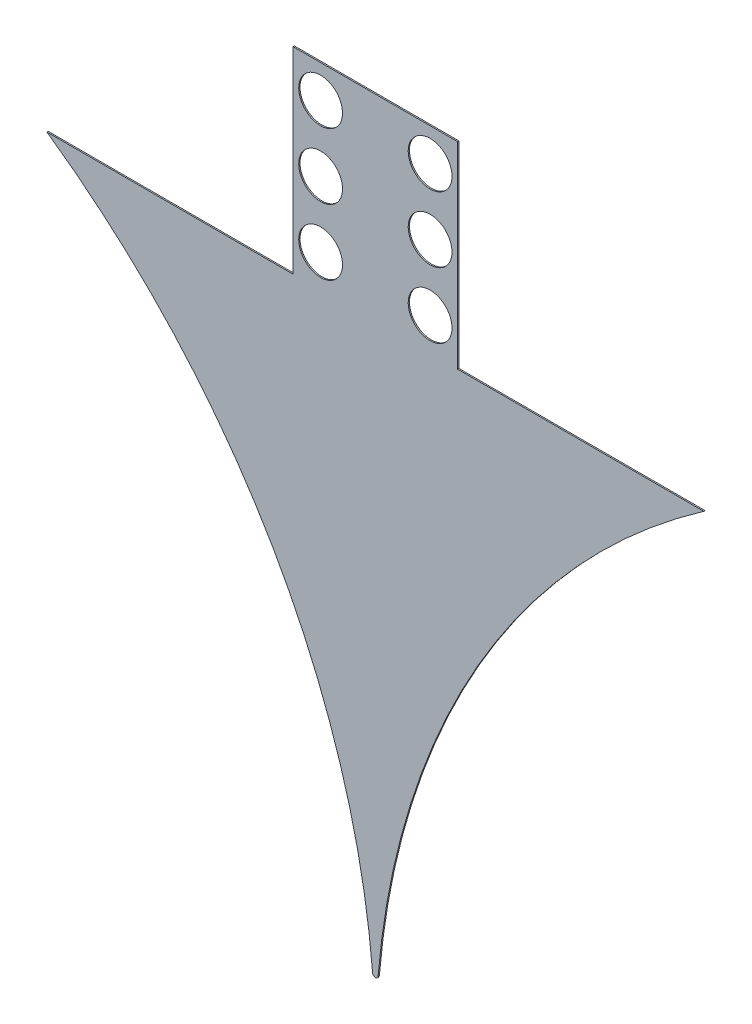
SolidWorks part; units mm, degrees
ref_plane "Front Plane" through (0, 0, 0) normal (0, 0, 1) x (1, 0, 0)
ref_plane "Top Plane" through (0, 0, 0) normal (0, 1, 0) x (1, 0, 0)
ref_plane "Right Plane" through (0, 0, 0) normal (1, 0, 0) x (0, 0, -1)
sketch "Sketch1" plane through (0, 0, 0) normal (0, 0, 1) x (1, 0, 0)
  line L0 (0, 145.9429) -> (0, -145.9429) construction
  line L1 (67, 50) -> (220, 50)
  line L2 (-67, 50) -> (-220, 50)
  line L3 (17.9555, 13) -> (15.1177, 40)
  line L4 (15.1177, 40) -> (12, 27.4955)
  line L5 (-15.1177, 40) -> (-12, 27.4955)
  line L6 (-17.9555, 13) -> (-15.1177, 40)
  line L7 (220, 50) -> (158.9525, 7.2541)
  line L8 (-220, 50) -> (-158.9525, 7.2541)
  line L9 (-140, -25) -> (-99.5632, -25)
  line L10 (140, -25) -> (99.5632, -25)
  arc A0 (67, 50) -> (17.9555, 13) centre (27.0477, 51.953) cw
  arc A1 (-67, 50) -> (-17.9555, 13) centre (-27.0477, 51.953) ccw
  arc A2 (12, 27.4955) -> (-12, 27.4955) centre (0, 0) ccw
  arc A3 (158.9525, 7.2541) -> (140, -25) centre (184.7635, -29.6077) ccw
  arc A4 (-99.5632, -25) -> (0, -115.6638) centre (-99.5632, -125) cw
  arc A5 (99.5632, -25) -> (0, -115.6638) centre (99.5632, -125) ccw
  arc A6 (-158.9525, 7.2541) -> (-140, -25) centre (-184.7635, -29.6077) cw
  dimension "D2" = 40
  dimension "D5" = 30
  dimension "D10" = 220
  dimension "D12" = 45
  dimension "D13" = 100
  dimension "D1" = 134
  dimension "D3" = 84
  dimension "D4" = 160
  dimension "D6" = 50
  dimension "D7" = 24
  dimension "D8" = 37
  dimension "D9" = 10
  dimension "D11" = 35
  dimension "D14" = 140
  dimension "D15" = 75
  dimension "D16" = 140
  dimension "D17" = 99.5632
sketch "Sketch2" plane through (0, 0, 0) normal (0, 0, 1) x (1, 0, 0)
  line L0 (0, 145.9429) -> (0, -145.9429) construction
  line L7 (0, 0) -> (0, -152.8683) construction
  line L8 (99.5632, -21.9265) -> (48.69, -83.15)
  line L9 (-99.5632, -21.9265) -> (-48.69, -83.15)
  line L26 (158.9525, 10.3276) -> (220, 53.0735)
  line L27 (220, 53.0735) -> (67, 53.0735)
  line L28 (17.9555, 16.0735) -> (15.1177, 43.0735)
  line L29 (15.1177, 43.0735) -> (12, 30.569)
  line L30 (-12, 30.569) -> (-15.1177, 43.0735)
  line L31 (-15.1177, 43.0735) -> (-17.9555, 16.0735)
  line L32 (-67, 53.0735) -> (-220, 53.0735)
  line L33 (-220, 53.0735) -> (-158.9525, 10.3276)
  line L34 (-140, -21.9265) -> (-99.5632, -21.9265)
  line L35 (99.5632, -21.9265) -> (140, -21.9265)
  circle A2 centre (46.19, 13) radius 1.5875
  circle A3 centre (-46.19, 13) radius 1.5875
  circle A4 centre (46.19, -80.65) radius 1.5875
  circle A5 centre (-46.19, -80.65) radius 1.5875
  arc A6 (48.69, -83.15) -> (0, -150) centre (70.2366, -150) ccw
  arc A7 (-48.69, -83.15) -> (0, -150) centre (-70.2366, -150) cw
  arc A14 (17.9555, 16.0735) -> (67, 53.0735) centre (27.0477, 55.0265) ccw
  arc A15 (12, 30.569) -> (-12, 30.569) centre (0, 3.0735) ccw
  arc A16 (-67, 53.0735) -> (-17.9555, 16.0735) centre (-27.0477, 55.0265) ccw
  arc A17 (-140, -21.9265) -> (-158.9525, 10.3276) centre (-184.7635, -26.5342) ccw
  arc A20 (158.9525, 10.3276) -> (140, -21.9265) centre (184.7635, -26.5342) ccw
  point P0 (0, 40)
  dimension "D3" = 93.65
  dimension "D4" = 3.175
  dimension "D5" = 3.175
  dimension "D6" = 3.175
  dimension "D7" = 3.175
  dimension "D2" = 40
  dimension "D9" = 25
  dimension "D10" = 46.19
  dimension "D11" = 27
  dimension "D12" = 46.19
  dimension "D13" = 99.5632
  dimension "D14" = 2.5
  dimension "D15" = 2.5
  dimension "D16" = 150
extrude "Boss-Extrude1" add sketch "Sketch2" along normal blind 0.118
sketch "Sketch3" plane through (0, 0, 0) normal (0, 0, -1) x (-1, 0, 0)
  line L0 (0, -121.719) -> (0, 0) construction
  line L1 (165, 49.5735) -> (165, 19.5735) construction
  line L2 (165, 19.5735) -> (165, 49.5735) construction
  line L3 (67, 53.0735) -> (220, 53.0735) construction
  circle A0 centre (165, 49.5735) radius 2
  circle A1 centre (165, 19.5735) radius 2
  circle A2 centre (150, 34.5735) radius 2
  dimension "D1" = 4
  dimension "D2" = 4
  dimension "D5" = 4
  dimension "D3" = 30
  dimension "D4" = 55
  dimension "D6" = 15
  dimension "D7" = 15
  dimension "D8" = 3.5
extrude "Cut-Extrude1" cut sketch "Sketch3" against normal through all
mirror "Mirror2" about plane through (0, 0, 0) normal (1, 0, 0) of "Cut-Extrude1"
chamfer "Chamfer1" distance 20 angle 90 2 edges at (-220, 53.0735, 0.059) (220, 53.0735, 0.059) first distance on face at (-143.5, 53.0735, 0.059) first distance on face at (143.5, 53.0735, 0.059)
sketch "Sketch4" plane through (0, 0, 0) normal (0, 0, -1) x (-1, 0, 0)
  line L11 (-225.9688, 80.922) -> (214.9402, 80.922)
  line L12 (-225.9688, 80.922) -> (-225.9688, -92.431)
  line L13 (-225.9688, -92.431) -> (214.9402, -92.431)
  line L14 (214.9402, 80.922) -> (214.9402, -92.431)
  point P0 (0, -150)
  dimension "D1" = 57.569
extrude "Cut-Extrude4" cut sketch "Sketch4" against normal through all contours L11 L14 L13 L12
sketch "Sketch5" plane through (0, 0, 0) normal (0, 0, -1) x (-1, 0, 0)
  line L0 (-30, -92.431) -> (30, -92.431) construction
  line L1 (-7.5, -74.431) -> (7.5, -74.431)
  line L2 (-7.5, -74.431) -> (-7.5, -92.431)
  line L3 (-7.5, -92.431) -> (7.5, -92.431)
  line L4 (7.5, -74.431) -> (7.5, -92.431)
  line L5 (-7.5, -74.431) -> (7.5, -92.431) construction
  line L6 (-7.5, -92.431) -> (7.5, -74.431) construction
  circle A0 centre (-5, -89.431) radius 2
  circle A1 centre (5, -89.431) radius 2
  circle A2 centre (-5, -83.431) radius 2
  circle A3 centre (5, -83.431) radius 2
  circle A4 centre (-5, -77.431) radius 2
  circle A5 centre (5, -77.431) radius 2
  point P0 (0, -83.431)
  dimension "D5" = 4
  dimension "D1" = 15
  dimension "D2" = 18
  dimension "D3" = 3
  dimension "D4" = 5
  dimension "D6" = 2
  dimension "D7" = 3
extrude "Boss-Extrude2" add sketch "Sketch5" against normal up to surface (0.118 mm away) up to face at (0, -109.1714, 0.118)
fillet "Fillet1" radius 0.25 1 edges at (0, -150, 0.059)
